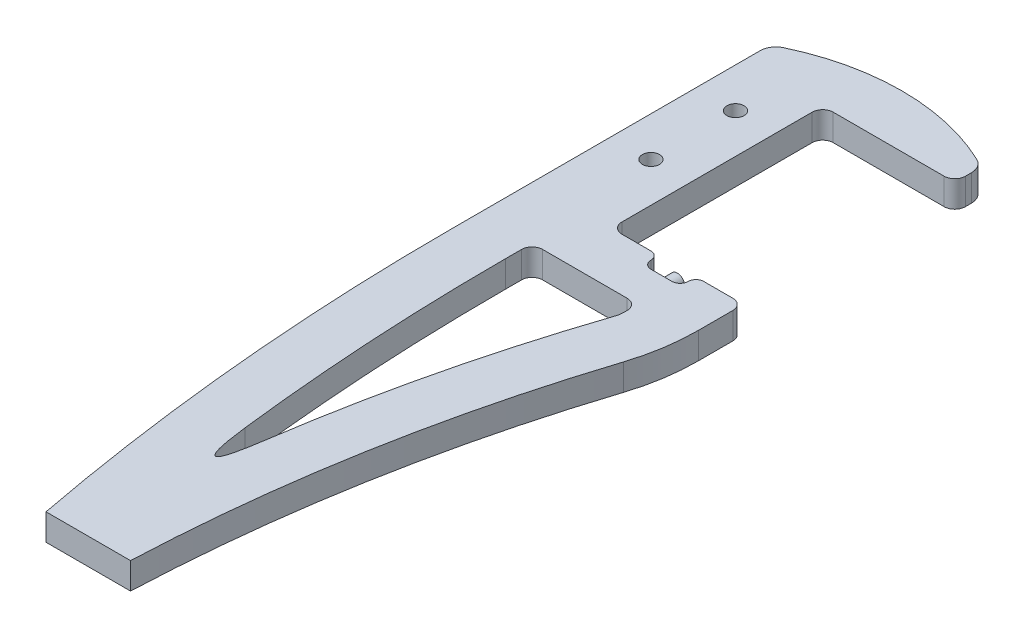
SolidWorks part; units mm, degrees
ref_plane "Front Plane" through (0, 0, 0) normal (0, 0, 1) x (1, 0, 0)
ref_plane "Top Plane" through (0, 0, 0) normal (0, 1, 0) x (1, 0, 0)
ref_plane "Right Plane" through (0, 0, 0) normal (1, 0, 0) x (0, 0, -1)
sketch "Sketch1" plane through (0, 0, 0) normal (0, 1, 0) x (1, 0, 0)
  line L0 (0, 145) -> (40, 145) construction
  line L1 (0, 0) -> (40, 0) construction
  line L2 (0, 0) -> (0, 150) construction
  line L3 (0, 150) -> (40, 150) construction
  line L4 (40, 0) -> (40, 150) construction
  line L5 (0, 145) -> (0, 85)
  line L6 (40, 145) -> (40, 140)
  line L7 (40, 140) -> (15, 140)
  line L8 (15, 140) -> (15, 100)
  line L9 (15, 100) -> (40, 100)
  line L10 (40, 100) -> (40, 85)
  line L11 (0, 85) -> (40, 85) construction
  line L12 (8, 0) -> (24, 0)
  arc A0 (0, 145) -> (40, 145) centre (20, 107.5) cw
  arc A1 (0, 85) -> (8, 0) centre (449.9997, 84.4764) ccw
  arc A2 (24, 0) -> (40, 85) centre (323.7429, -12.4163) cw
  dimension "D10" = 300
  dimension "D11" = 450
  dimension "D1" = 150
  dimension "D2" = 40
  dimension "D3" = 5
  dimension "D4" = 60
  dimension "D5" = 5
  dimension "D6" = 15
  dimension "D7" = 25
  dimension "D8" = 8
  dimension "D9" = 16
extrude "Boss-Extrude1" add sketch "Sketch1" along normal blind 5
sketch "Sketch2" plane through (0, 5, 0) normal (0, 1, 0) x (1, 0, 0)
  line L0 (7.5, 142.7174) -> (7.5, 98.3016) construction
  circle A0 centre (7.5, 131) radius 1.625
  circle A1 centre (7.5, 115) radius 1.625
  dimension "D2" = 3.25
  dimension "D3" = 3.25
  dimension "D1" = 7.5
  dimension "D4" = 9
  dimension "D5" = 16
extrude "Cut-Extrude1" cut sketch "Sketch2" against normal up to surface (5 mm away) up to face at (21.69, 0, -94.5389)
sketch "Sketch3" plane through (0, 5, 0) normal (0, 1, 0) x (1, 0, 0)
  line L0 (24, 100) -> (24, 97)
  line L1 (40, 100) -> (15, 100) construction
  line L2 (24, 97) -> (31, 97)
  line L3 (31, 97) -> (31, 100)
  line L4 (24, 100) -> (31, 100)
  dimension "D1" = 9
  dimension "D2" = 9
  dimension "D3" = 3
extrude "Cut-Extrude2" cut sketch "Sketch3" against normal up to surface (5 mm away) up to face at (7.5, 0, -116.625)
sketch "Sketch4" plane through (0, 0, -97) normal (0, 0, -1) x (-1, 0, 0)
  line L0 (-24, 2.5) -> (-31, 2.5) construction
  line L1 (-24, 0) -> (-24, 5) construction
  line L2 (-31, 0) -> (-31, 5) construction
  line L3 (-27.5, 5) -> (-27.5, 0) construction
  line L4 (-24, 5) -> (-31, 5) construction
  line L5 (-24, 0) -> (-31, 0) construction
  circle A0 centre (-27.5, 2.5) radius 1.375
  dimension "D1" = 2.75
extrude "Boss-Extrude2" add sketch "Sketch4" along normal blind 3
sketch "Sketch5" plane through (0, 5, 0) normal (0, 1, 0) x (1, 0, 0)
  line L1 (14, 90) -> (30, 90)
  line L3 (14, 87) -> (30, 87) construction
  line L4 (30, 90) -> (30, 87)
  line L22 (30, 87) -> (14, 87)
  line L23 (14, 87) -> (14, 90)
  line L24 (14, 90) -> (10, 90)
  line L25 (10, 90) -> (10, 84.9942)
  line L26 (30, 86.6548) -> (30, 87)
  line L29 (14, 90) -> (10, 90)
  line L30 (10, 90) -> (10, 84.9942)
  line L31 (30, 86.6548) -> (30, 87)
  arc A6 (10, 84.9942) -> (15.1657, 17.2499) centre (449.9997, 84.4764) ccw
  arc A7 (30, 86.6548) -> (15.1657, 17.2499) centre (323.7429, -12.4163) ccw
  arc A8 (10, 84.9942) -> (15.1657, 17.2499) centre (449.9997, 84.4764) ccw
  arc A9 (30, 86.6548) -> (15.1657, 17.2499) centre (323.7429, -12.4163) ccw
  dimension "D1" = 10
extrude "Cut-Extrude3" cut sketch "Sketch5" against normal up to surface (5 mm away) up to face at (23.35, 0, -95.6707)
fillet "Fillet1" radius 2 2 edges at (30, 2.5, -90) (10, 2.5, -90)
fillet "Fillet2" radius 4 1 edges at (30, 2.5, -86.6548)
fillet "Fillet3" radius 40 1 edges at (40, 2.5, -85)
fillet "Fillet5" radius 2 2 edges at (15, 2.5, -100) (15, 2.5, -140)
fillet "Fillet6" radius 2 2 edges at (40, 2.5, -100) (40, 2.5, -140)
fillet "Fillet7" radius 3 2 edges at (0, 2.5, -145) (40, 2.5, -145)
fillet "Fillet8" radius 2 1 edges at (15.1657, 2.5, -17.2499)
fillet "Fillet10" radius 1.5 4 edges at (31, 2.5, -100) (31, 2.5, -97) (24, 2.5, -97) (24, 2.5, -100)
